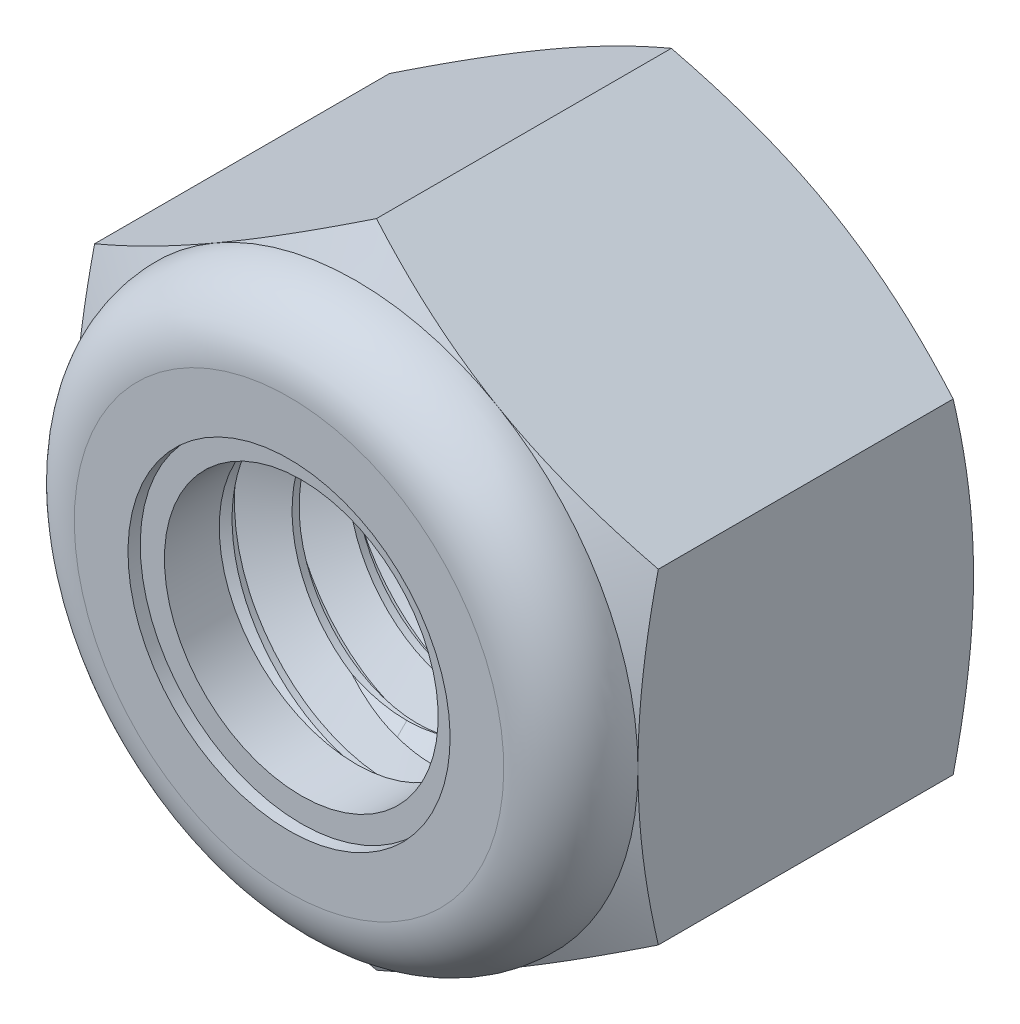
SolidWorks part; units mm, degrees
ref_plane "Front Plane" through (0, 0, 0) normal (0, 0, 1) x (1, 0, 0)
ref_plane "Top Plane" through (0, 0, 0) normal (0, 1, 0) x (1, 0, 0)
ref_plane "Right Plane" through (0, 0, 0) normal (1, 0, 0) x (0, 0, -1)
sketch "Sketch1" plane through (0, 0, 0) normal (1, 0, 0) x (0, 0, -1)
  line L0 (0, 3.5) -> (0, -3.5) construction
  line L1 (-2.5, 2) -> (2.5, 2)
  line L2 (-2.5, 0) -> (2.5, 0) construction
  line L3 (-2.5, -3.5) -> (2.5, -3.5)
  line L4 (-2.5, -3.5) -> (-2.5, 3.5)
  line L5 (-2.5, 3.5) -> (2.5, 3.5)
  line L6 (2.5, -3.5) -> (2.5, 3.5)
  line L7 (-2.5, -2) -> (2.5, -2)
  line L8 (2.4563, 2.0758) -> (3.1563, 2.0758) construction
  line L9 (3.1563, 2.0758) -> (2.8063, 1.4696) construction
  line L10 (2.8063, 1.4696) -> (2.4563, 2.0758) construction
  line L11 (2.8063, 1.4696) -> (2.8063, 1.5453) construction
  line L12 (2.5, 2) -> (3.1125, 2) construction
  line L13 (2.8063, 2) -> (2.8063, 2.0758) construction
  line L15 (3.1344, 2.0379) -> (2.4781, 2.0379) construction
  line L17 (2.7625, 1.5453) -> (2.85, 1.5453) construction
  point P20 (2.8063, 2.0379)
  dimension "Thread Size" = 4
  dimension "Thread Pitch" = 0.7
  dimension "D1" = 0.0875
  dimension "Width" = 7
  dimension "Height" = 5
sketch "Sketch2" plane through (0, 0, 0) normal (1, 0, 0) x (0, 0, -1)
  line L0 (2.325, 2) -> (2.5, 2.175)
  line L1 (-2.5, 2) -> (2.5, 2) construction
  line L2 (2.5, -3.5) -> (2.5, 3.5) construction
  line L3 (-2.5, 0) -> (2.5, 0) construction
  line L4 (-2.5, 0) -> (2.5, 0) construction
  line L5 (-2.5, 2.6667) -> (-2.5, 2)
  line L6 (-2.5, -3.5) -> (-2.5, 3.5) construction
  line L7 (-2.5, 2) -> (-2.3476, 2)
  line L8 (-1.6667, 3.3476) -> (-1.6667, 2.175)
  line L9 (-2.5, 3.5) -> (2.5, 3.5) construction
  line L10 (-1.6667, 3.5) -> (2.5, 3.5)
  line L11 (2.5, 3.5) -> (2.5, 2.175)
  line L12 (-2.3476, 2.6667) -> (-2.3476, 2)
  line L13 (-1.4917, 2) -> (2.325, 2)
  line L14 (2.5, 2.175) -> (2.5, 2) construction
  line L15 (2.5, 2) -> (2.325, 2) construction
  line L16 (-1.6667, 2.175) -> (-1.4917, 2)
  line L17 (-1.6667, 2.175) -> (2.5, 2.175) construction
  line L18 (-2.3476, 2) -> (-2.3476, 1.7) construction
  line L19 (-2.3476, 1.7) -> (-1.6667, 1.7) construction
  line L20 (-1.6667, 1.7) -> (-1.6667, 2.175) construction
  line L21 (-1.6667, 3.5) -> (2.5, 12.4354) construction
  arc A0 (-1.6667, 3.5) -> (-2.5, 2.6667) centre (-1.6667, 2.6667) ccw
  arc A1 (-1.6667, 3.3476) -> (-2.3476, 2.6667) centre (-1.6667, 2.6667) ccw
  dimension "D1" = 0.8333
  dimension "D3" = 0.1524
  dimension "D4" = 0.175
  dimension "D2" = 3.4
  dimension "D5" = 25
revolve "Revolve1" add sketch "Sketch2" angle 360 about L4
sketch "Sketch3" plane through (0, 0, 0) normal (0, 0, -1) x (-1, 0, 0)
  line L0 (1.2021, 1.2021) -> (-1.2021, -1.2021) construction
  line L1 (3.5, 2.0207) -> (0, 4.0415)
  line L2 (0, 4.0415) -> (-3.5, 2.0207)
  line L3 (-3.5, 2.0207) -> (-3.5, -2.0207)
  line L4 (-3.5, -2.0207) -> (0, -4.0415)
  line L5 (0, -4.0415) -> (3.5, -2.0207)
  line L6 (3.5, -2.0207) -> (3.5, 2.0207)
  line L8 (-1.2021, 1.2021) -> (1.2021, -1.2021) construction
  circle A0 centre (0, 0) radius 3.5 construction
  circle A1 centre (0, 0) radius 3.3476
  circle A2 centre (0, 0) radius 1.7 construction
extrude "Boss-Extrude1" add sketch "Sketch3" along normal up to surface (2.5 mm away) from vertex up to face at (0, -3.5, -2.5) starting at point (0, 3.3476, 1.6667)
sketch "Sketch4" plane through (0, 0, 0) normal (1, 0, 0) x (0, 0, -1)
  line L0 (-1.6667, 3.5) -> (-0.5307, 5.9361)
  line L1 (-1.6667, 3.5) -> (2.5, 12.4354) construction
  line L2 (-0.5307, 5.9361) -> (1.364, 5.9361)
  line L4 (1.364, 5.9361) -> (2.5, 3.5)
  line L5 (0.4167, 4.0415) -> (0.4167, 5.9361) construction
  line L6 (2.5, 4.0415) -> (-1.6667, 4.0415) construction
  line L7 (-1.6667, 3.5) -> (-1.6667, 6.6361)
  line L8 (-1.6667, 6.6361) -> (2.5, 6.6361)
  line L9 (2.5, 6.6361) -> (2.5, 3.5)
  line L10 (0.4167, 5.9361) -> (0.4167, 6.6361) construction
  line L11 (2.4563, 2.0758) -> (3.1563, 2.0758) construction
revolve "Cut-Revolve1" cut sketch "Sketch4" angle 360 about L2
sketch "Sketch5" plane through (0, 0, 0) normal (1, 0, 0) x (0, 0, -1)
  line L0 (-2.3476, 2) -> (-2.3476, 1.7) construction
  line L1 (-2.3476, 1.7) -> (-1.6667, 1.7) construction
  line L2 (-1.6667, 1.7) -> (-1.6667, 2.175) construction
  line L3 (-2.3476, 2.6667) -> (-2.3476, 1.7)
  line L4 (-2.3476, 1.7) -> (-1.6667, 1.7)
  line L5 (-1.6667, 1.7) -> (-1.6667, 3.3476)
  arc A0 (-1.6667, 3.3476) -> (-2.3476, 2.6667) centre (-1.6667, 2.6667) ccw construction
  arc A1 (-1.6667, 3.3476) -> (-2.3476, 2.6667) centre (-1.6667, 2.6667) ccw
revolve "Revolve2" add sketch "Sketch5" angle 360 about L4
sketch "Sketch6" plane through (0, 0, -2.5) normal (0, 0, -1) x (-1, 0, 0)
  circle A0 centre (0, 0) radius 2
ref_axis "Center Axis 1" through (0, 0, 2.5) along (0, 0, -1)
curve "Helix/Spiral1" pitch 0.7 height 5 radius 2 centre (0, 0, -2.5) axis (0, 0, 1) start towards (0, 1, 0)
sketch "Sketch7" plane through (0, 0, 0) normal (1, 0, 0) x (0, 0, -1)
  line L0 (3.1344, 2.0379) -> (2.4781, 2.0379) construction
  line L1 (2.7625, 1.5453) -> (2.85, 1.5453) construction
  line L2 (3.1563, 2.0758) -> (2.8063, 1.4696) construction
  line L3 (2.8063, 1.4696) -> (2.4563, 2.0758) construction
  line L4 (3.1344, 2.0379) -> (2.4781, 2.0379)
  line L5 (2.7625, 1.5453) -> (2.85, 1.5453)
  line L6 (3.1344, 2.0379) -> (2.85, 1.5453)
  line L7 (2.7625, 1.5453) -> (2.4781, 2.0379)
sweep "Sweep1" add profiles "Sketch7" path "Helix/Spiral1"
sketch "Sketch8" plane through (0, 0, 0) normal (1, 0, 0) x (0, 0, -1)
  line L0 (-2.5, 2) -> (-2.5, 3.5)
  line L1 (-2.3476, 2.6667) -> (-2.3476, 2) construction
  line L2 (-2.5, 3.5) -> (-7.5, 3.5)
  line L3 (-2.3476, 2.6667) -> (-2.3476, 2)
  line L4 (-1.6667, 2.175) -> (-1.4917, 2) construction
  line L5 (-1.6667, 2.175) -> (-0.9612, 1.4696)
  line L6 (2.8063, 1.4696) -> (-7.5, 1.4696) construction
  line L7 (-1.6667, 2.175) -> (-1.6667, 3.3476)
  line L8 (-2.5, 3.5) -> (2.5, 3.5) construction
  line L10 (-2.3476, 2) -> (-2.5, 2)
  line L12 (-7.5, 0) -> (-0.9612, 0)
  line L13 (-2.5, 0) -> (2.5, 0) construction
  line L14 (-0.9612, 0) -> (-0.9612, 1.4696)
  line L15 (2.325, 2) -> (2.5, 2.175) construction
  line L16 (1.7946, 1.4696) -> (2.5, 2.175)
  line L17 (1.7946, 1.4696) -> (1.7946, 0)
  line L18 (1.7946, 0) -> (3.5063, 0)
  line L19 (3.5063, 0) -> (3.5063, 2.175)
  line L20 (3.5063, 2.175) -> (2.5, 2.175)
  line L21 (-7.5, 0) -> (-7.5, 3.5)
  line L23 (2.8063, 1.4696) -> (3.5063, 1.4696) construction
  line L24 (2.4563, 2.0758) -> (3.1563, 2.0758) construction
  arc A0 (-1.6667, 3.3476) -> (-2.3476, 2.6667) centre (-1.6667, 2.6667) ccw construction
  arc A1 (-1.6667, 3.3476) -> (-2.3476, 2.6667) centre (-1.6667, 2.6667) ccw
revolve "Cut-Revolve2" cut sketch "Sketch8" angle 360 about L2
equation "\"D1@Sketch1\"=\"Thread Pitch@Sketch1\"/8"
equation "\"D1@Sketch2\"=\"Height@Sketch1\"/6"
equation "\"D4@Sketch2\"=.25*\"Thread Pitch@Sketch1\""
equation "\"D2@Sketch2\"=.85*\"Thread Size@Sketch1\""
equation "\"D4@Helix/Spiral1\"=\"Thread Pitch@Sketch1\""
equation "\"D3@Helix/Spiral1\"=\"Height@Sketch1\""
